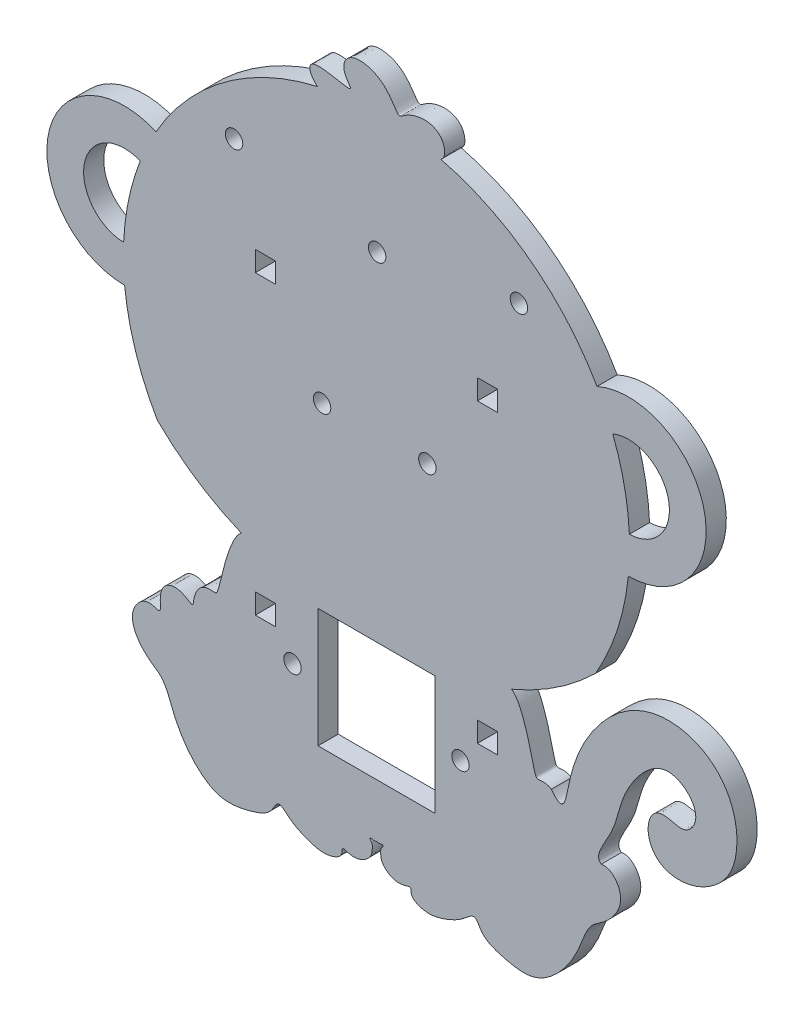
SolidWorks part; units mm, degrees
ref_plane "Front Plane" through (0, 0, 0) normal (0, 0, 1) x (1, 0, 0)
ref_plane "Top Plane" through (0, 0, 0) normal (0, 1, 0) x (1, 0, 0)
ref_plane "Right Plane" through (0, 0, 0) normal (1, 0, 0) x (0, 0, -1)
sketch "Model" plane through (0, 0, 0) normal (0, 0, 1) x (1, 0, 0)
  line L0 (-354.7776, 349.4226) -> (-354.7776, 392.0292) construction
  line L1 (-368.5276, 390.0292) -> (-368.5276, 362.0292)
  line L2 (-368.5276, 390.0292) -> (-341.0276, 390.0292)
  line L21 (-354.7776, 390.0292) -> (-354.7776, 362.0292)
  line L26 (-368.5276, 362.0292) -> (-341.0276, 362.0292)
  line L27 (-341.0276, 390.0292) -> (-341.0276, 362.0292)
  line L28 (-378.5276, 381.2792) -> (-383.2776, 381.2792)
  line L29 (-331.0276, 386.0292) -> (-326.2776, 386.0292)
  line L30 (-331.0276, 386.0292) -> (-331.0276, 381.2792)
  line L31 (-331.0276, 381.2792) -> (-326.2776, 381.2792)
  line L32 (-326.2776, 386.0292) -> (-326.2776, 381.2792)
  line L33 (-383.2776, 386.0292) -> (-383.2776, 381.2792)
  line L34 (-378.5276, 386.0292) -> (-383.2776, 386.0292)
  line L35 (-378.5276, 386.0292) -> (-378.5276, 381.2792)
  line L36 (-326.2776, 451.0292) -> (-331.0276, 451.0292) construction
  line L37 (-326.2776, 455.7792) -> (-326.2776, 451.0292) construction
  line L38 (-331.0276, 455.7792) -> (-331.0276, 451.0292) construction
  line L39 (-326.2776, 455.7792) -> (-331.0276, 455.7792) construction
  line L40 (-383.2776, 451.0292) -> (-378.5276, 451.0292) construction
  line L41 (-383.2776, 455.7792) -> (-383.2776, 451.0292) construction
  line L42 (-378.5276, 455.7792) -> (-378.5276, 451.0292) construction
  line L43 (-383.2776, 455.7792) -> (-378.5276, 455.7792) construction
  line L44 (-326.2776, 451.0292) -> (-331.0276, 451.0292)
  line L45 (-326.2776, 455.7792) -> (-326.2776, 451.0292)
  line L46 (-331.0276, 455.7792) -> (-331.0276, 451.0292)
  line L47 (-326.2776, 455.7792) -> (-331.0276, 455.7792)
  line L48 (-383.2776, 451.0292) -> (-378.5276, 451.0292)
  line L49 (-383.2776, 455.7792) -> (-383.2776, 451.0292)
  line L50 (-378.5276, 455.7792) -> (-378.5276, 451.0292)
  line L51 (-383.2776, 455.7792) -> (-378.5276, 455.7792)
  line L52 (-397.2776, 416.2792) -> (-402.0276, 416.2792) construction
  line L53 (-312.2776, 421.0292) -> (-307.5276, 421.0292) construction
  line L54 (-312.2776, 421.0292) -> (-312.2776, 416.2792) construction
  line L55 (-312.2776, 416.2792) -> (-307.5276, 416.2792) construction
  line L56 (-307.5276, 421.0292) -> (-307.5276, 416.2792) construction
  line L57 (-402.0276, 421.0292) -> (-402.0276, 416.2792) construction
  line L58 (-397.2776, 421.0292) -> (-402.0276, 421.0292) construction
  line L59 (-397.2776, 421.0292) -> (-397.2776, 416.2792) construction
  circle A0 centre (-295.506, 451.3512) radius 18.2563
  circle A1 centre (-295.506, 451.3512) radius 9.6191
  circle A2 centre (-414.0491, 451.3512) radius 9.6191
  circle A3 centre (-414.0491, 451.3512) radius 18.2562
  arc A4 (-354.7776, 392.0292) -> (-303.2483, 409.4214) centre (-346.9752, 453.9435) ccw
  arc A5 (-303.2483, 409.4214) -> (-354.7776, 497.7106) centre (-353.9365, 439.0196) ccw
  arc A6 (-354.7776, 497.7106) -> (-406.3069, 409.4214) centre (-355.6187, 439.0196) ccw
  arc A7 (-406.3069, 409.4214) -> (-354.7776, 392.0292) centre (-362.58, 453.9435) ccw
  circle A17 centre (-388.2776, 475.7792) radius 2.05
  circle A18 centre (-321.2776, 475.7792) radius 2.05
  circle A19 centre (-374.5276, 375.7792) radius 2.05
  circle A20 centre (-335.0276, 375.7792) radius 2.05
  circle A24 centre (-342.8132, 432.3712) radius 1.7
  circle A25 centre (-367.5781, 432.2899) radius 1.7
  circle A26 centre (-354.6192, 469.5436) radius 1.7
  circle A27 centre (-367.5781, 432.2899) radius 2.05
  circle A28 centre (-342.8132, 432.3712) radius 2.05
  circle A29 centre (-354.6192, 469.5436) radius 2.05
  spline S0 degree 5 poles (-386.5513, 396.3273) (-386.9161, 396.0792) (-387.366, 395.6344) (-387.8968, 394.8986) (-388.5033, 393.7572) (-389.1715, 392.131) (-389.5779, 391.0147) (-389.9703, 389.8193) (-390.4193, 388.3234) (-390.8333, 386.8049) (-391.2016, 385.3464) (-391.5167, 384.0353) (-391.7817, 382.9443) (-391.9754, 382.2094) (-392.154, 381.6648) (-392.3367, 381.3111) (-392.5515, 381.1299) (-392.8335, 381.0822) (-393.2115, 381.1155) (-393.6934, 381.1695) (-394.2612, 381.1826) (-394.881, 381.0994) (-395.5104, 380.8776) (-396.1059, 380.4945) (-396.6315, 379.9559) (-397.064, 379.2975) (-397.3921, 378.574) (-397.6173, 377.8496) (-397.7535, 377.1888) (-397.8274, 376.647) (-397.8791, 376.2603) (-397.9596, 376.0385) (-398.1148, 375.9725) (-398.366, 376.0408) (-398.7069, 376.2147) (-399.1201, 376.4601) (-399.5915, 376.7412) (-400.118, 377.0223) (-400.6998, 377.2689) (-401.4638, 377.484) (-402.3002, 377.5538) (-403.1741, 377.4267) (-404.0022, 377.0659) (-404.6982, 376.4644) (-405.1535, 375.8118) (-405.4613, 375.0322) (-405.6199, 374.1669) (-405.658, 373.2789) (-405.6265, 372.4425) (-405.5875, 371.7311) (-405.6037, 371.2053) (-405.7274, 370.9008) (-405.9901, 370.8167) (-406.3911, 370.9021) (-406.9056, 371.0748) (-407.4962, 371.2433) (-408.1222, 371.3275) (-408.7511, 371.2827) (-409.3596, 371.0975) (-409.9312, 370.7828) (-410.4544, 370.3635) (-410.9212, 369.8697) (-411.3251, 369.3269) (-411.6596, 368.7503) (-411.9191, 368.1478) (-412.0987, 367.5224) (-412.1944, 366.8744) (-412.2033, 366.204) (-412.0922, 365.2374) (-411.7958, 364.2405) (-411.2536, 363.0979) (-410.5055, 362.004) (-409.6286, 361.0209) (-408.9407, 360.363) (-408.2617, 359.7955) (-407.7193, 359.3836) (-407.2138, 359.0282) (-406.7532, 358.7179) (-406.3372, 358.4326) (-405.9584, 358.1461) (-405.6064, 357.8322) (-405.2709, 357.469) (-404.9452, 357.0452) (-404.6288, 356.5637) (-404.3252, 356.0366) (-404.0394, 355.4808) (-403.7755, 354.9137) (-403.4863, 354.2349) (-403.2244, 353.5638) (-402.972, 352.8931) (-402.7045, 352.203) (-402.4017, 351.478) (-402.0626, 350.7211) (-401.6746, 349.928) (-401.239, 349.111) (-400.7631, 348.2898) (-400.2543, 347.482) (-399.7226, 346.693) (-399.1634, 345.9321) (-398.5743, 345.1992) (-397.9495, 344.4888) (-397.2819, 343.7971) (-396.6937, 343.2329) (-395.9467, 342.5739) (-395.1459, 341.9478) (-394.2909, 341.3752) (-393.3842, 340.8821) (-392.43, 340.4917) (-391.606, 340.244) (-390.756, 340.0794) (-389.8831, 339.9983) (-388.9906, 339.995) (-388.0822, 340.0607) (-387.1626, 340.184) (-386.2377, 340.3533) (-385.315, 340.5579) (-384.404, 340.7898) (-383.5163, 341.0454) (-382.6665, 341.327) (-381.8713, 341.6429) (-381.1468, 342.0028) (-380.5061, 342.4143) (-379.9577, 342.8796) (-379.5022, 343.3918) (-379.1308, 343.9312) (-378.8219, 344.461) (-378.5447, 344.9321) (-378.2678, 345.2959) (-377.9655, 345.5144) (-377.6259, 345.571) (-377.2571, 345.4813) (-376.8758, 345.2788) (-376.4963, 345.0025) (-376.1171, 344.6823) (-375.7208, 344.3352) (-375.2832, 343.9706) (-374.7791, 343.5936) (-374.1903, 343.2075) (-373.3777, 342.7411) (-372.4498, 342.2849) (-371.4489, 341.8618) (-370.4344, 341.4969) (-369.4571, 341.2116) (-368.6859, 341.0352) (-367.9644, 340.9249) (-367.2855, 340.8811) (-366.6359, 340.9021) (-366.0015, 340.9842) (-365.3739, 341.1239) (-364.7563, 341.3185) (-364.1709, 341.5681) (-363.6579, 341.8743) (-363.2584, 342.2351) (-362.9996, 342.6398) (-362.8828, 343.0653) (-362.8624, 343.4679) (-362.8603, 343.7943) (-362.8008, 344.002) (-362.6453, 344.0822) (-362.4039, 344.0645) (-362.091, 343.9838) (-361.7122, 343.8689) (-361.2711, 343.747) (-360.7722, 343.6434) (-360.2251, 343.5846) (-359.6439, 343.594) (-359.0456, 343.6889) (-358.3311, 343.9146) (-357.653, 344.2718) (-357.0557, 344.716) (-356.5775, 345.1787) (-356.2334, 345.621) (-356.0331, 345.9754) (-355.9027, 346.3429) (-355.8208, 346.7573) (-355.7698, 347.2366) (-355.7451, 347.7596) (-355.7624, 348.2488) (-355.8386, 348.6234) (-355.9777, 348.8376) (-356.1508, 348.9418) (-356.2927, 349.0757) (-356.3365, 349.2881) (-356.2363, 349.4431) (-355.9971, 349.4554) (-355.6775, 349.3823) (-355.3456, 349.3188) (-355.1001, 349.3199) (-354.9324, 349.357) (-354.828, 349.398) (-354.7776, 349.4226) knots 0 0 0 0 0 0 0.02 0.025 0.03 0.035 0.04 0.045 0.05 0.06 0.065 0.07 0.075 0.08 0.085 0.09 0.095 0.1 0.105 0.11 0.115 0.12 0.125 0.13 0.135 0.14 0.145 0.15 0.155 0.16 0.165 0.17 0.175 0.18 0.185 0.19 0.195 0.2 0.205 0.21 0.22 0.225 0.23 0.235 0.24 0.245 0.25 0.255 0.26 0.265 0.27 0.275 0.28 0.285 0.29 0.295 0.3 0.305 0.31 0.315 0.32 0.325 0.33 0.335 0.34 0.345 0.35 0.355 0.36 0.375 0.38 0.39 0.395 0.4 0.405 0.41 0.415 0.42 0.425 0.43 0.435 0.44 0.445 0.45 0.455 0.46 0.465 0.47 0.48 0.485 0.49 0.495 0.5 0.51 0.515 0.52 0.525 0.53 0.54 0.545 0.55 0.555 0.56 0.565 0.575 0.58 0.585 0.59 0.595 0.6 0.605 0.61 0.615 0.62 0.625 0.63 0.635 0.64 0.645 0.65 0.655 0.66 0.665 0.67 0.675 0.68 0.685 0.69 0.695 0.7 0.705 0.71 0.715 0.72 0.725 0.73 0.735 0.74 0.745 0.755 0.76 0.765 0.77 0.775 0.78 0.785 0.79 0.795 0.8 0.805 0.81 0.815 0.82 0.825 0.83 0.835 0.84 0.845 0.85 0.855 0.86 0.865 0.87 0.875 0.88 0.885 0.89 0.895 0.905 0.91 0.915 0.92 0.925 0.93 0.935 0.94 0.945 0.95 0.955 0.96 0.965 0.97 0.975 0.98 0.985 0.99 0.995 1 1 1 1 1 1 weights 1 1 1 1 1 1 1 1 1 1 1 1 1 1 1 1 1 1 1 1 1 1 1 1 1 1 1 1 1 1 1 1 1 1 1 1 1 1 1 1 1 1 1 1 1 1 1 1 1 1 1 1 1 1 1 1 1 1 1 1 1 1 1 1 1 1 1 1 1 1 1 1 1 1 1 1 1 1 1 1 1 1 1 1 1 1 1 1 1 1 1 1 1 1 1 1 1 1 1 1 1 1 1 1 1 1 1 1 1 1 1 1 1 1 1 1 1 1 1 1 1 1 1 1 1 1 1 1 1 1 1 1 1 1 1 1 1 1 1 1 1 1 1 1 1 1 1 1 1 1 1 1 1 1 1 1 1 1 1 1 1 1 1 1 1 1 1 1 1 1 1 1 1 1 1 1 1 1 1 1 1 1 1 1 1 1 1 1 1 1 1
  spline S1 degree 5 poles (-323.0039, 396.3273) (-322.6391, 396.0792) (-322.1892, 395.6344) (-321.6584, 394.8986) (-321.0519, 393.7572) (-320.3837, 392.131) (-319.9773, 391.0147) (-319.5849, 389.8193) (-319.1359, 388.3234) (-318.7219, 386.8049) (-318.3536, 385.3464) (-318.0385, 384.0353) (-317.7735, 382.9443) (-317.5798, 382.2094) (-317.4012, 381.6648) (-317.2185, 381.3111) (-317.0037, 381.1299) (-316.7217, 381.0822) (-316.3437, 381.1155) (-315.8618, 381.1695) (-315.294, 381.1826) (-314.6741, 381.0994) (-314.0448, 380.8776) (-313.4493, 380.4945) (-312.9237, 379.9559) (-312.4912, 379.2975) (-312.1631, 378.574) (-311.9379, 377.8496) (-311.8017, 377.1888) (-311.7278, 376.647) (-311.6761, 376.2603) (-311.5956, 376.0385) (-311.4404, 375.9725) (-311.1892, 376.0408) (-310.8483, 376.2147) (-310.4351, 376.4601) (-309.9637, 376.7412) (-309.4372, 377.0223) (-308.8554, 377.2689) (-308.0914, 377.484) (-307.2549, 377.5538) (-306.3811, 377.4267) (-305.553, 377.0659) (-304.857, 376.4644) (-304.4017, 375.8118) (-304.0939, 375.0322) (-303.9353, 374.1669) (-303.8972, 373.2789) (-303.9287, 372.4425) (-303.9677, 371.7311) (-303.9515, 371.2053) (-303.8278, 370.9008) (-303.5651, 370.8167) (-303.1641, 370.9021) (-302.6496, 371.0748) (-302.0589, 371.2433) (-301.433, 371.3275) (-300.8041, 371.2827) (-300.1956, 371.0975) (-299.624, 370.7828) (-299.1008, 370.3635) (-298.634, 369.8697) (-298.2301, 369.3269) (-297.8956, 368.7503) (-297.6361, 368.1478) (-297.4565, 367.5224) (-297.3608, 366.8744) (-297.3519, 366.204) (-297.463, 365.2374) (-297.7594, 364.2405) (-298.3016, 363.0979) (-299.0496, 362.004) (-299.9266, 361.0209) (-300.6145, 360.363) (-301.2935, 359.7955) (-301.8359, 359.3836) (-302.3414, 359.0282) (-302.8019, 358.7179) (-303.218, 358.4326) (-303.5968, 358.1461) (-303.9488, 357.8322) (-304.2843, 357.469) (-304.61, 357.0452) (-304.9264, 356.5637) (-305.23, 356.0366) (-305.5158, 355.4808) (-305.7797, 354.9137) (-306.0689, 354.2349) (-306.3308, 353.5638) (-306.5832, 352.8931) (-306.8507, 352.203) (-307.1535, 351.478) (-307.4926, 350.7211) (-307.8805, 349.928) (-308.3162, 349.111) (-308.7921, 348.2898) (-309.3008, 347.482) (-309.8326, 346.693) (-310.3918, 345.9321) (-310.9809, 345.1992) (-311.6057, 344.4888) (-312.2733, 343.7971) (-312.8615, 343.2329) (-313.6085, 342.5739) (-314.4093, 341.9478) (-315.2643, 341.3752) (-316.171, 340.8821) (-317.1251, 340.4917) (-317.9492, 340.244) (-318.7992, 340.0794) (-319.6721, 339.9983) (-320.5646, 339.995) (-321.473, 340.0607) (-322.3926, 340.184) (-323.3175, 340.3533) (-324.2402, 340.5579) (-325.1512, 340.7898) (-326.0389, 341.0454) (-326.8887, 341.327) (-327.6839, 341.6429) (-328.4084, 342.0028) (-329.049, 342.4143) (-329.5975, 342.8796) (-330.053, 343.3918) (-330.4244, 343.9312) (-330.7333, 344.461) (-331.0105, 344.9321) (-331.2874, 345.2959) (-331.5897, 345.5144) (-331.9293, 345.571) (-332.298, 345.4813) (-332.6794, 345.2788) (-333.0589, 345.0025) (-333.4381, 344.6823) (-333.8343, 344.3352) (-334.272, 343.9706) (-334.7761, 343.5936) (-335.3649, 343.2075) (-336.1775, 342.7411) (-337.1053, 342.2849) (-338.1063, 341.8618) (-339.1207, 341.4969) (-340.0981, 341.2116) (-340.8693, 341.0352) (-341.5908, 340.9249) (-342.2697, 340.8811) (-342.9193, 340.9021) (-343.5537, 340.9842) (-344.1813, 341.1239) (-344.7989, 341.3185) (-345.3842, 341.5681) (-345.8972, 341.8743) (-346.2968, 342.2351) (-346.5556, 342.6398) (-346.6724, 343.0653) (-346.6928, 343.4679) (-346.6949, 343.7943) (-346.7544, 344.002) (-346.9099, 344.0822) (-347.1513, 344.0645) (-347.4642, 343.9838) (-347.843, 343.8689) (-348.2841, 343.747) (-348.783, 343.6434) (-349.33, 343.5846) (-349.9113, 343.594) (-350.5096, 343.6889) (-351.2241, 343.9146) (-351.9022, 344.2718) (-352.4995, 344.716) (-352.9777, 345.1787) (-353.3218, 345.621) (-353.5221, 345.9754) (-353.6525, 346.3429) (-353.7344, 346.7573) (-353.7854, 347.2366) (-353.8101, 347.7596) (-353.7928, 348.2488) (-353.7166, 348.6234) (-353.5775, 348.8376) (-353.4043, 348.9418) (-353.2625, 349.0757) (-353.2187, 349.2881) (-353.3188, 349.4431) (-353.5581, 349.4554) (-353.8776, 349.3823) (-354.2096, 349.3188) (-354.4551, 349.3199) (-354.6228, 349.357) (-354.7272, 349.398) (-354.7776, 349.4226) knots 0 0 0 0 0 0 0.02 0.025 0.03 0.035 0.04 0.045 0.05 0.06 0.065 0.07 0.075 0.08 0.085 0.09 0.095 0.1 0.105 0.11 0.115 0.12 0.125 0.13 0.135 0.14 0.145 0.15 0.155 0.16 0.165 0.17 0.175 0.18 0.185 0.19 0.195 0.2 0.205 0.21 0.22 0.225 0.23 0.235 0.24 0.245 0.25 0.255 0.26 0.265 0.27 0.275 0.28 0.285 0.29 0.295 0.3 0.305 0.31 0.315 0.32 0.325 0.33 0.335 0.34 0.345 0.35 0.355 0.36 0.375 0.38 0.39 0.395 0.4 0.405 0.41 0.415 0.42 0.425 0.43 0.435 0.44 0.445 0.45 0.455 0.46 0.465 0.47 0.48 0.485 0.49 0.495 0.5 0.51 0.515 0.52 0.525 0.53 0.54 0.545 0.55 0.555 0.56 0.565 0.575 0.58 0.585 0.59 0.595 0.6 0.605 0.61 0.615 0.62 0.625 0.63 0.635 0.64 0.645 0.65 0.655 0.66 0.665 0.67 0.675 0.68 0.685 0.69 0.695 0.7 0.705 0.71 0.715 0.72 0.725 0.73 0.735 0.74 0.745 0.755 0.76 0.765 0.77 0.775 0.78 0.785 0.79 0.795 0.8 0.805 0.81 0.815 0.82 0.825 0.83 0.835 0.84 0.845 0.85 0.855 0.86 0.865 0.87 0.875 0.88 0.885 0.89 0.895 0.905 0.91 0.915 0.92 0.925 0.93 0.935 0.94 0.945 0.95 0.955 0.96 0.965 0.97 0.975 0.98 0.985 0.99 0.995 1 1 1 1 1 1 weights 1 1 1 1 1 1 1 1 1 1 1 1 1 1 1 1 1 1 1 1 1 1 1 1 1 1 1 1 1 1 1 1 1 1 1 1 1 1 1 1 1 1 1 1 1 1 1 1 1 1 1 1 1 1 1 1 1 1 1 1 1 1 1 1 1 1 1 1 1 1 1 1 1 1 1 1 1 1 1 1 1 1 1 1 1 1 1 1 1 1 1 1 1 1 1 1 1 1 1 1 1 1 1 1 1 1 1 1 1 1 1 1 1 1 1 1 1 1 1 1 1 1 1 1 1 1 1 1 1 1 1 1 1 1 1 1 1 1 1 1 1 1 1 1 1 1 1 1 1 1 1 1 1 1 1 1 1 1 1 1 1 1 1 1 1 1 1 1 1 1 1 1 1 1 1 1 1 1 1 1 1 1 1 1 1 1 1 1 1 1 1
  spline S2 degree 5 poles (-313.6608, 380.6036) (-313.4447, 380.3201) (-313.0302, 379.8091) (-312.4617, 379.2104) (-311.8099, 378.7481) (-311.1658, 378.7209) (-310.6734, 379.2168) (-310.2927, 380.1782) (-309.9686, 381.5239) (-309.6406, 383.1622) (-309.2509, 385.0015) (-308.7553, 386.9633) (-308.0017, 389.3938) (-307.0301, 391.8531) (-305.8363, 394.2764) (-304.438, 396.6235) (-302.856, 398.8596) (-301.4232, 400.6299) (-299.5708, 402.6142) (-297.5538, 404.3848) (-295.3743, 405.8881) (-292.6508, 407.2693) (-289.33, 408.2696) (-286.299, 408.5941) (-283.2651, 408.3445) (-280.3791, 407.5391) (-278.0928, 406.4785) (-276.3489, 405.3668) (-274.4851, 403.7878) (-272.9371, 401.946) (-271.7278, 399.9069) (-270.8571, 397.7451) (-270.3065, 395.5388) (-270.0462, 393.71) (-269.965, 391.9301) (-270.041, 390.2346) (-270.2523, 388.6524) (-270.5799, 387.2019) (-271.0097, 385.8888) (-271.5359, 384.701) (-272.1612, 383.6109) (-272.8958, 382.5869) (-273.7555, 381.6014) (-274.7609, 380.6417) (-275.9355, 379.7174) (-277.2973, 378.8569) (-278.8515, 378.1044) (-280.5823, 377.5164) (-282.4459, 377.1586) (-284.3607, 377.1036) (-286.2191, 377.417) (-287.9032, 378.1427) (-289.299, 379.2867) (-290.311, 380.8037) (-290.8776, 382.5789) (-290.9832, 384.4209) (-290.6506, 386.112) (-289.936, 387.4514) (-288.9223, 388.2997) (-287.7148, 388.6275) (-286.4328, 388.5495) (-285.1876, 388.2576) (-284.0619, 387.9667) (-283.0865, 387.8525) (-282.2242, 388) (-281.4248, 388.4326) (-280.673, 389.1343) (-280.0427, 390.0762) (-279.6515, 391.2145) (-279.6146, 392.4895) (-279.9934, 393.8227) (-280.764, 395.118) (-281.8511, 396.2738) (-283.152, 397.1938) (-284.5629, 397.798) (-286.0086, 398.0348) (-287.4505, 397.8849) (-288.8706, 397.3556) (-290.2614, 396.4772) (-291.6143, 395.2987) (-292.9061, 393.8845) (-294.101, 392.3076) (-295.162, 390.6429) (-296.0582, 388.9596) (-296.775, 387.314) (-297.3214, 385.7431) (-297.7428, 384.2552) (-298.1147, 382.8324) (-298.5188, 381.4451) (-299.0233, 380.0639) (-299.6638, 378.6704) (-300.4174, 377.2729) (-301.2032, 375.907) (-301.9108, 374.6227) (-302.4229, 373.4731) (-302.6383, 372.5046) (-302.5279, 371.8953) (-302.2784, 371.535) (-302.0378, 371.3378) (-301.8989, 371.25) knots 0 0 0 0 0 0 0.01 0.02 0.03 0.04 0.05 0.06 0.07 0.08 0.09 0.1 0.11 0.13 0.14 0.15 0.16 0.17 0.18 0.2 0.21 0.22 0.24 0.26 0.27 0.28 0.29 0.3 0.31 0.33 0.34 0.35 0.36 0.37 0.38 0.39 0.4 0.41 0.42 0.43 0.44 0.45 0.46 0.47 0.48 0.49 0.5 0.51 0.52 0.53 0.54 0.55 0.56 0.57 0.58 0.59 0.6 0.61 0.62 0.63 0.64 0.65 0.66 0.67 0.68 0.69 0.7 0.71 0.72 0.73 0.74 0.75 0.76 0.77 0.78 0.79 0.8 0.81 0.82 0.83 0.84 0.85 0.86 0.87 0.88 0.89 0.9 0.91 0.92 0.93 0.94 0.95 0.96 0.97 0.98 0.99 1 1 1 1 1 1 weights 1 1 1 1 1 1 1 1 1 1 1 1 1 1 1 1 1 1 1 1 1 1 1 1 1 1 1 1 1 1 1 1 1 1 1 1 1 1 1 1 1 1 1 1 1 1 1 1 1 1 1 1 1 1 1 1 1 1 1 1 1 1 1 1 1 1 1 1 1 1 1 1 1 1 1 1 1 1 1 1 1 1 1 1 1 1 1 1 1 1 1 1 1 1 1 1 1 1 1 1
  spline S3 degree 5 poles (-368.6485, 496.2522) (-368.7445, 496.3189) (-368.9332, 496.4614) (-369.2068, 496.7025) (-369.5526, 497.079) (-369.9454, 497.6352) (-370.274, 498.2589) (-370.4903, 498.915) (-370.5107, 499.5416) (-370.2384, 500.0643) (-369.5991, 500.4175) (-368.5716, 500.5624) (-367.2236, 500.5088) (-365.6871, 500.3043) (-364.1304, 500.0214) (-362.7304, 499.745) (-361.6458, 499.5606) (-360.9878, 499.5411) (-360.7964, 499.7361) (-361.0037, 500.1558) (-361.4562, 500.7754) (-361.9696, 501.5464) (-362.3683, 502.407) (-362.5408, 503.2925) (-362.4544, 504.1433) (-362.127, 504.907) (-361.609, 505.5429) (-360.9624, 506.0248) (-360.2377, 506.3463) (-359.4651, 506.519) (-358.6621, 506.5638) (-357.8368, 506.5034) (-356.9934, 506.3554) (-356.1367, 506.1232) (-355.2752, 505.7947) (-354.4199, 505.3529) (-353.5839, 504.7839) (-352.7824, 504.0858) (-352.0321, 503.2767) (-351.3511, 502.4053) (-350.7568, 501.5504) (-350.2591, 500.8009) (-349.8549, 500.2405) (-349.5224, 499.9306) (-349.215, 499.8941) (-348.8555, 500.0985) (-348.3621, 500.4755) (-347.6717, 500.9383) (-346.77, 501.4022) (-345.6888, 501.7923) (-344.4899, 502.0451) (-343.2539, 502.1125) (-342.0666, 501.9648) (-341.0067, 501.594) (-340.1326, 501.0174) (-339.4704, 500.2805) (-339.0219, 499.4471) (-338.7725, 498.5899) (-338.6988, 497.7804) (-338.776, 497.0807) (-338.9866, 496.5313) (-339.2553, 496.2274) (-339.5119, 496.0787) (-339.7073, 496.0148) (-339.8111, 495.9917) knots 0 0 0 0 0 0 0.016667 0.033333 0.05 0.066667 0.083333 0.1 0.116667 0.133333 0.15 0.166667 0.183333 0.2 0.216667 0.233333 0.25 0.266667 0.283333 0.3 0.316667 0.333333 0.35 0.366667 0.383333 0.4 0.416667 0.433333 0.45 0.466667 0.483333 0.5 0.516667 0.533333 0.55 0.566667 0.583333 0.6 0.616667 0.633333 0.65 0.666667 0.683333 0.7 0.716667 0.733333 0.75 0.766667 0.783333 0.8 0.816667 0.833333 0.85 0.866667 0.883333 0.9 0.916667 0.933333 0.95 0.966667 0.983333 1 1 1 1 1 1 weights 1 1 1 1 1 1 1 1 1 1 1 1 1 1 1 1 1 1 1 1 1 1 1 1 1 1 1 1 1 1 1 1 1 1 1 1 1 1 1 1 1 1 1 1 1 1 1 1 1 1 1 1 1 1 1 1 1 1 1 1 1 1 1 1 1
  dimension "D10" = 4.1
  dimension "D12" = 20
  dimension "D15" = 4.1
  dimension "D4" = 4.1
  dimension "D5" = 4.1
  dimension "D6" = 4.1
  dimension "D2" = 13.75
  dimension "D3" = 2
  dimension "D1" = 28
  dimension "D7" = 4.75
  dimension "D8" = 4
  dimension "D9" = 10
  dimension "D11" = 5
  dimension "D13" = 30
  dimension "D14" = 14
  dimension "D16" = 5.5
  dimension "D17" = 4
extrude "Boss-Extrude1" add sketch "Model" along normal blind 4.75 contours S3 A6 A5 | A6 A7 A4 A5 A0 A3 L47 L45 L44 L46 L49 L51 L50 L48 A17 A18 | A1 A5 A0 | A1 A5 | A5 A1 A0 | A6 A3 A2 | A3 A6 A2 | S2 S1 A4 A7 S0 L34 L35 L28 L33 L29 L32 L31 L30 L2 L27 L26 L1 A19 A20 | S2 S1 | A2 A6 region at (-282.9239, 438.7463, 0) region at (-305.5348, 449.2347, 0) region at (-354.7766, 441.9829, 0) region at (-300.18, 450.3648, 0) region at (-354.5371, 500.3437, 0) region at (-320.1153, 387.0345, 0) region at (-409.0425, 464.3935, 0) region at (-404.0204, 449.2347, 0) region at (-409.3752, 450.3648, 0) region at (-274.0272, 382.186, 0)
